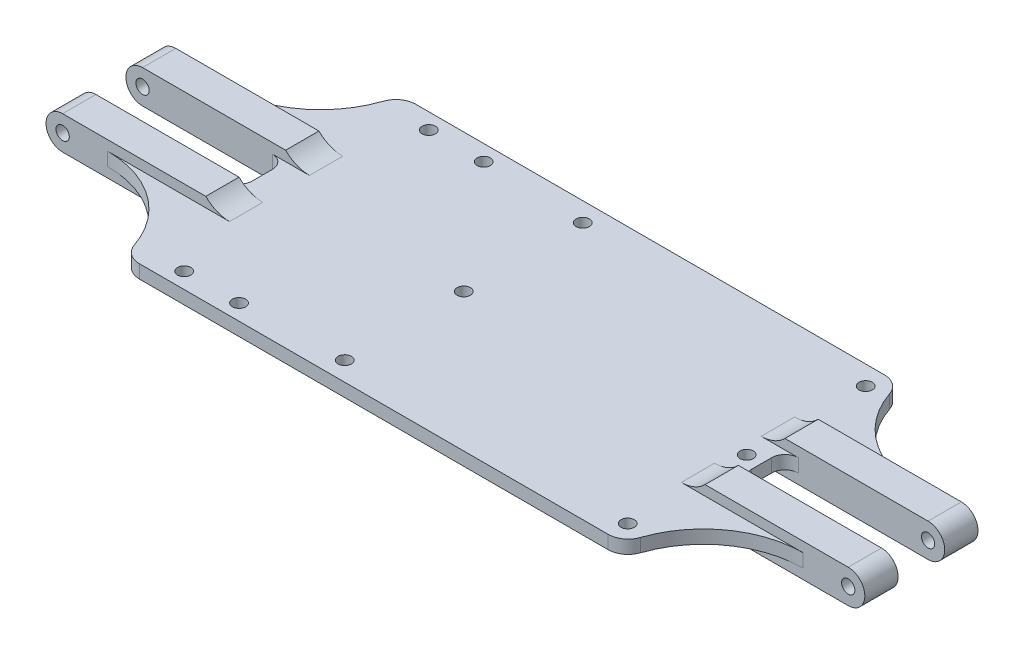
SolidWorks part; units mm, degrees
ref_plane "Front Plane" through (0, 0, 0) normal (0, 0, 1) x (1, 0, 0)
ref_plane "Top Plane" through (0, 0, 0) normal (0, 1, 0) x (1, 0, 0)
ref_plane "Right Plane" through (0, 0, 0) normal (1, 0, 0) x (0, 0, -1)
sketch "Sketch1" plane through (0, 0, 0) normal (0, 1, 0) x (1, 0, 0)
  line L0 (0, 121.3543) -> (0, -121.3543) construction
  line L1 (-75, -41.5) -> (75, -41.5)
  line L2 (-75, -41.5) -> (-75, 41.5)
  line L3 (-75, 41.5) -> (75, 41.5)
  line L4 (75, -41.5) -> (75, 41.5)
  line L5 (-75, -41.5) -> (75, 41.5) construction
  line L6 (-75, 41.5) -> (75, -41.5) construction
  line L7 (-246.33, 0) -> (246.33, 0) construction
  line L8 (-75, 7) -> (-124, 7)
  line L9 (-124, 7) -> (-124, 17)
  line L10 (-124, 17) -> (-75, 17)
  line L11 (-124, -17) -> (-75, -17)
  line L12 (-124, -7) -> (-124, -17)
  line L13 (-75, -7) -> (-124, -7)
  line L14 (-118, 46.0679) -> (-118, -44.6537) construction
  line L15 (124, -17) -> (75, -17)
  line L16 (124, -7) -> (124, -17)
  line L17 (75, -7) -> (124, -7)
  line L18 (75, 7) -> (124, 7)
  line L19 (124, 7) -> (124, 17)
  line L20 (124, 17) -> (75, 17)
  circle A0 centre (70.5, 35.75) radius 2
  circle A1 centre (70.5, 0) radius 2
  circle A2 centre (70.5, -35.75) radius 2
  circle A3 centre (-14.5, -35.75) radius 2
  circle A4 centre (-14.5, 0) radius 2
  circle A5 centre (-14.5, 35.75) radius 2
  point P0 (0, 0)
  point P8 (0, 0)
  point P11 (0, 0)
  dimension "D7" = 4
  dimension "D8" = 4
  dimension "D9" = 4
  dimension "D10" = 4
  dimension "D11" = 4
  dimension "D12" = 4
  dimension "D1" = 83
  dimension "D2" = 150
  dimension "D3" = 14
  dimension "D4" = 10
  dimension "D5" = 43
  dimension "D6" = 6
extrude "Boss-Extrude1" add sketch "Sketch1" along normal mid plane 10 contours L10 L9 L8 L2 | L2 L13 L12 L11 | L19 L20 L4 L18 | L17 L4 L15 L16 region at (-99.5, 0, 12) region at (99.5, 0, 12) region at (-99.5, 0, -12) region at (99.5, 0, -12)
sketch "Sketch2" plane through (0, 0, -17) normal (0, 0, -1) x (-1, 0, 0)
  line L0 (-124, -5) -> (-75, -5) construction
  line L1 (-124, 5) -> (-75, 5) construction
  line L2 (-124, 5) -> (-124, -5) construction
  line L6 (0, 69.849) -> (0, -80.9232) construction
  line L10 (-118, 5) -> (-118, 9.5057)
  line L11 (-118, 9.5057) -> (-152.7264, 9.5057)
  line L12 (-152.7264, 9.5057) -> (-152.7264, -6.9043)
  line L13 (-152.7264, -6.9043) -> (-118, -6.9043)
  line L14 (-118, -6.9043) -> (-118, -5)
  line L15 (118, 5) -> (118, 9.5057)
  line L16 (118, 9.5057) -> (152.7264, 9.5057)
  line L17 (152.7264, 9.5057) -> (152.7264, -6.9043)
  line L18 (152.7264, -6.9043) -> (118, -6.9043)
  line L19 (118, -6.9043) -> (118, -5)
  arc A0 (-118, -5) -> (-118, 5) centre (-118, 0) cw
  circle A1 centre (-118, 0) radius 2
  circle A2 centre (118, 0) radius 2
  arc A3 (118, -5) -> (118, 5) centre (118, 0) ccw
  dimension "D2" = 4
  dimension "D1" = 6
extrude "Cut-Extrude7" cut sketch "Sketch2" against normal through all both and the other way through all
extrude "Boss-Extrude2" add sketch "Sketch1<3>" along normal mid plane 4 contours L1 L4 L3 L2 region at (-0.1706, 0, 0)
sketch "Sketch1<3>" plane through (0, 0, 0) normal (0, 1, 0) x (1, 0, 0) same geometry as "Sketch1"
fillet "Fillet1" radius 10 4 edges at (-75, 2, -12) (-75, 2, 12) (75, 2, -12) (75, 2, 12)
sketch "Sketch3" plane through (0, -2, 0) normal (0, -1, 0) x (1, 0, 0)
  line L0 (-75, 17) -> (75, 17)
  line L1 (-75, 7) -> (75, 7)
  line L2 (-75, -7) -> (75, -7)
  line L3 (-75, -17) -> (75, -17)
  line L4 (-75, -17) -> (-75, -7)
  line L5 (75, -17) -> (75, -7)
  line L6 (75, 7) -> (75, 17)
  line L7 (-75, 7) -> (-75, 17)
extrude "Boss-Extrude3" add sketch "Sketch3" along normal up to surface (3 mm away) up to face at (96.5, -5, 13.25)
fillet "Fillet2" radius 30 4 edges at (-75, 0, 17) (-75, 0, -17) (75, 0, 17) (75, 0, -17)
fillet "Fillet3" radius 4 4 edges at (75, 0, 7) (75, 0, -7) (-75, 0, 7) (-75, 0, -7)
fillet "Fillet4" radius 6 4 edges at (75, 0, 41.5) (-75, 0, 41.5) (75, 0, -41.5) (-75, 0, -41.5)
sketch "Sketch4" plane through (0, 2, 0) normal (0, 1, 0) x (1, 0, 0)
  circle A0 centre (-45.25, -36.75) radius 2
  circle A1 centre (-61.75, -36.75) radius 2
  circle A2 centre (-45.25, 36.75) radius 2
  circle A3 centre (-61.75, 36.75) radius 2
extrude "Cut-Extrude8" cut sketch "Sketch4" against normal through all both and the other way through all
